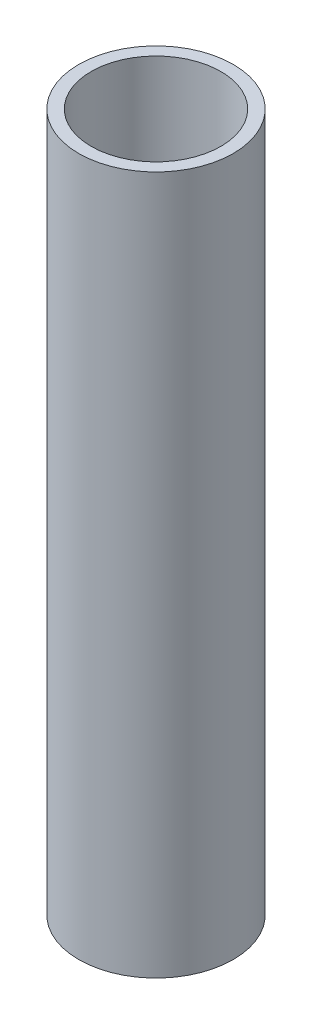
SolidWorks part; units mm, degrees
ref_plane "Front Plane" through (0, 0, 0) normal (0, 0, 1) x (1, 0, 0)
ref_plane "Top Plane" through (0, 0, 0) normal (0, 1, 0) x (1, 0, 0)
ref_plane "Right Plane" through (0, 0, 0) normal (1, 0, 0) x (0, 0, -1)
sketch "Sketch1" plane through (0, 0, 0) normal (0, 1, 0) x (1, 0, 0)
  circle A0 centre (0, 0) radius 12.5
  circle A1 centre (0, 0) radius 10.5
  dimension "D1" = 25
  dimension "D2" = 21
extrude "Boss-Extrude1" add sketch "Sketch1" along normal blind 113
equation "\"cf_tube_outer_diameter\" = 25mm"
equation "\"cf_tube_inner_diameter\" = 21mm"
equation "\"mid_plate_mid_to_top\" = 100mm"
equation "\"mid_plate_mid_to_bottom\" = 100mm"
equation "\"mid_plate_horizontal_spacing\" = 250mm"
equation "\"cf_plate_thickness\" = 4mm"
equation "\"mid_tube_length\" = 500mm"
equation "\"D1@Sketch1\"=\"cf_tube_outer_diameter\""
equation "\"D2@Sketch1\"=\"cf_tube_inner_diameter\""
